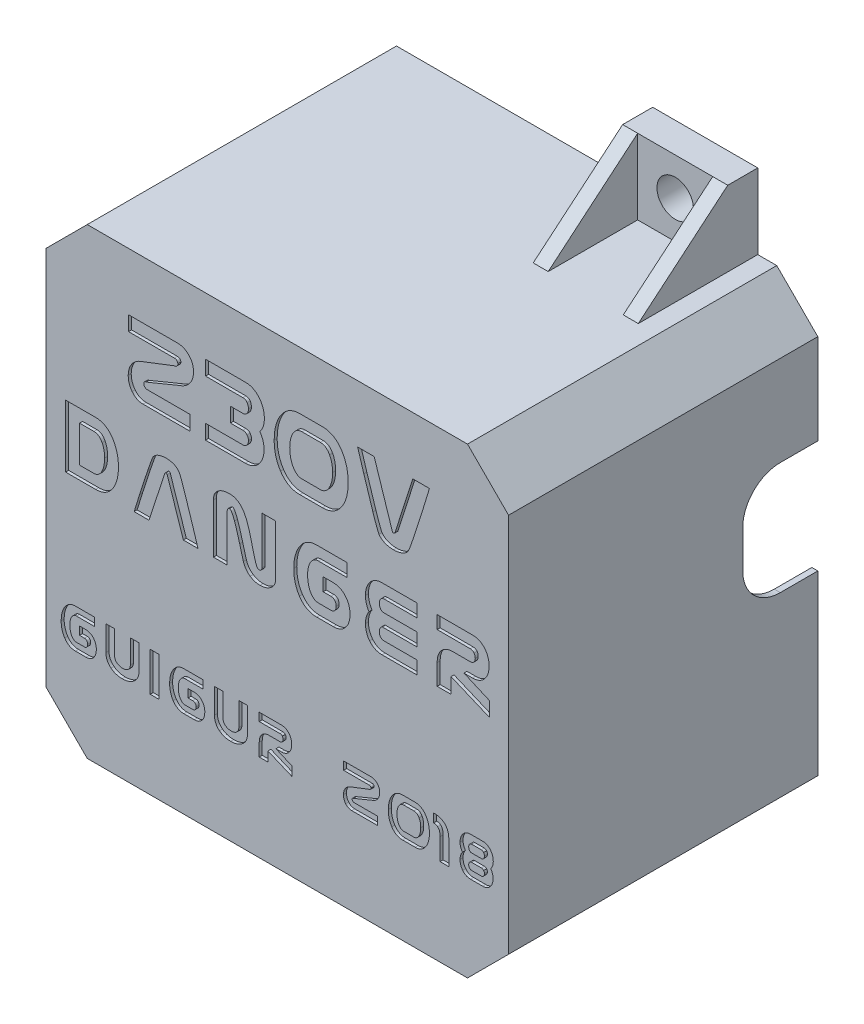
SolidWorks part; units mm, degrees
ref_plane "Plan de face" through (0, 0, 0) normal (0, 0, 1) x (1, 0, 0)
ref_plane "Plan de dessus" through (0, 0, 0) normal (0, 1, 0) x (1, 0, 0)
ref_plane "Plan de droite" through (0, 0, 0) normal (1, 0, 0) x (0, 0, -1)
sketch "Esquisse1" plane through (0, 0, 0) normal (0, 0, 1) x (1, 0, 0)
  line L0 (0.8, -55.8) -> (5.8, -60.8)
  line L1 (0, 0) -> (61.6, 0)
  line L2 (0, 0) -> (0, -61.6)
  line L3 (0, -61.6) -> (61.6, -61.6)
  line L4 (61.6, 0) -> (61.6, -61.6)
  line L5 (0.8, -0.8) -> (60.8, -0.8)
  line L6 (0.8, -0.8) -> (0.8, -60.8)
  line L7 (0.8, -60.8) -> (60.8, -60.8)
  line L8 (60.8, -0.8) -> (60.8, -60.8)
  line L9 (55.8, -60.8) -> (60.8, -55.8)
  line L10 (55.8, -0.8) -> (60.8, -5.8)
  line L11 (0.8, -5.8) -> (5.8, -0.8)
  line L12 (56.1314, 0) -> (61.6, -5.4686)
  line L13 (56.1314, -61.6) -> (61.6, -56.1314)
  line L14 (5.4686, -61.6) -> (0, -56.1314)
  line L15 (0, -5.4686) -> (5.4686, 0)
  dimension "D1" = 0.8
  dimension "D2" = 60
  dimension "D3" = 60
  dimension "D4" = 0.8
  dimension "D5" = 0.8
  dimension "D6" = 0.8
  dimension "D7" = 45
  dimension "D8" = 5
  dimension "D9" = 0.8
  dimension "D10" = 5
  dimension "D11" = 45
  dimension "D12" = 0.8
  dimension "D13" = 5
  dimension "D14" = 5
  dimension "D15" = 0.8
  dimension "D16" = 0.8
extrude "Boss.-Extru.1" add sketch "Esquisse1" along normal blind 40 contours L15 L2 L14 L6 | L14 L7 L0 L6 | L14 L3 L13 L7 | L7 L13 L8 L9 | L8 L13 L4 L12 | L12 L5 L10 L8 | L15 L5 L12 L1 | L15 L6 L11 L5 region at (0.4021, -30.8, 0) region at (3.0292, -58.5708, 0) region at (30.8, -61.1979, 0) region at (3.0292, -3.0292, 0) region at (58.5708, -58.5708, 0) region at (30.8, -0.4021, 0) region at (61.1979, -30.8, 0) region at (58.5708, -3.0292, 0)
sketch "Esquisse2" plane through (0, 0, 40) normal (0, 0, 1) x (1, 0, 0)
  line L0 (56.1314, 0) -> (61.6, -5.4686)
  line L1 (0, 0) -> (61.6, 0)
  line L2 (0, 0) -> (0, -61.6)
  line L3 (0, -61.6) -> (61.6, -61.6)
  line L4 (61.6, 0) -> (61.6, -61.6)
  line L5 (61.6, -56.1314) -> (56.1314, -61.6)
  line L6 (5.4686, -61.6) -> (0, -56.1314)
  line L7 (0, -5.4686) -> (5.4686, 0)
  line M5 (56.1314, -61.6) -> (61.6, -56.1314)
  line M6 (61.6, -56.1314) -> (61.6, -5.4686)
  line M7 (61.6, -5.4686) -> (56.1314, 0)
  line M8 (56.1314, 0) -> (5.4686, 0)
  line M9 (5.4686, 0) -> (0, -5.4686)
  line M10 (0, -5.4686) -> (0, -56.1314)
  line M11 (0, -56.1314) -> (5.4686, -61.6)
  line M12 (5.4686, -61.6) -> (56.1314, -61.6)
  line M13 (60.8, -5.8) -> (60.8, -55.8)
  line M14 (60.8, -55.8) -> (55.8, -60.8)
  line M15 (55.8, -60.8) -> (5.8, -60.8)
  line M16 (5.8, -60.8) -> (0.8, -55.8)
  line M17 (0.8, -55.8) -> (0.8, -5.8)
  line M18 (0.8, -5.8) -> (5.8, -0.8)
  line M19 (5.8, -0.8) -> (55.8, -0.8)
  line M20 (55.8, -0.8) -> (60.8, -5.8)
  dimension "D1" = 61.6
  dimension "D2" = 61.6
extrude "Boss.-Extru.2" add sketch "Esquisse2" along normal blind 1.2 contours M13 M20 M19 M18 M17 M16 M15 M14 | M12 M5 M6 M7 M8 M9 M10 M11 M20 M13 M14 M15 M16 M17 M18 M19 region at (58.8041, -2.7959, 40) region at (30.8, -30.8, 40)
sketch "Esquisse3" plane through (61.6, 0, 0) normal (1, 0, 0) x (0, 0, -1)
  line L0 (0, -5.4686) -> (0, -56.1314) construction
  line L1 (0, -32.5) -> (-5, -32.5)
  line L2 (0, -32.5) -> (0, -17.5)
  line L3 (0, -17.5) -> (-5, -17.5)
  line L4 (-10, -27.5) -> (-10, -22.5)
  arc A0 (-5, -32.5) -> (-10, -27.5) centre (-5, -27.5) cw
  arc A1 (-5, -17.5) -> (-10, -22.5) centre (-5, -22.5) ccw
  point P8 (-10, -32.5)
  point P11 (-10, -17.5)
  point P12 (0, -25)
  dimension "D3" = 5
  dimension "D1" = 15
  dimension "D2" = 10
  dimension "D4" = 25
extrude "Enlèv. mat.-Extru.1" cut sketch "Esquisse3" against normal blind 0.8
sketch "Esquisse4" plane through (0, -61.6, 0) normal (0, -1, 0) x (1, 0, 0)
  line L0 (5.4686, 0) -> (56.1314, 0) construction
  line L1 (23.3, 0) -> (38.3, 0)
  line L2 (23.3, 0) -> (23.3, 20)
  line L3 (28.3, 25) -> (33.3, 25)
  line L4 (38.3, 0) -> (38.3, 20)
  line L5 (5.4686, 41.2) -> (56.1314, 41.2) construction
  arc A0 (38.3, 20) -> (33.3, 25) centre (33.3, 20) ccw
  arc A1 (28.3, 25) -> (23.3, 20) centre (28.3, 20) ccw
  point P6 (30.8, 25)
  point P9 (30.8, 41.2)
  point P14 (23.3, 25)
  dimension "D3" = 5
  dimension "D1" = 25
  dimension "D2" = 15
extrude "Enlèv. mat.-Extru.2" cut sketch "Esquisse4" against normal blind 0.8
sketch "Esquisse5" plane through (0, 0, 41.2) normal (0, 0, 1) x (1, 0, 0)
  line L0 (0, -17) -> (61.6, -17) construction
  line L1 (0, -5.4686) -> (0, -56.1314) construction
  line L2 (61.6, -56.1314) -> (61.6, -5.4686) construction
  line L3 (0, -30) -> (61.6, -30) construction
  line L4 (56.1314, 0) -> (5.4686, 0) construction
  line L5 (0, -50) -> (61.6, -50) construction
  text T0 "230V" font "Nasalization" height in points 36
  text T1 "DANGER" font "Nasalization" height in points 32
  text T2 "GUIGUR 2018" font "Nasalization" height in points 20
  dimension "D1" = 17
  dimension "D2" = 30
  dimension "D3" = 50
extrude "Enlèv. mat.-Extru.3" cut sketch "Esquisse5" against normal blind 0.4
ref_plane "Plan1" through (56.1314, 0, 0) normal (1, 0, 0) x (0, 0, -1)
sketch "Esquisse7" plane through (0, 0, 0) normal (0, 0, -1) x (-1, 0, 0)
  line L0 (-5.4686, 0) -> (-56.1314, 0) construction
  line L1 (-51.6, 0) -> (-41.6, 0)
  line L2 (-51.6, 0) -> (-51.6, 10)
  line L3 (-51.6, 10) -> (-41.6, 10)
  line L4 (-41.6, 0) -> (-41.6, 10)
  circle A0 centre (-46.6, 5) radius 2.4316
  point P6 (-46.6, 10)
  point P10 (-41.6, 5)
  dimension "D1" = 10
  dimension "D2" = 10
  dimension "D3" = 15
extrude "Boss.-Extru.3" add sketch "Esquisse7" against normal blind 4
ref_plane "Plan2" through (46.6, 0, 0) normal (1, 0, 0) x (0, 0, -1)
sketch "Esquisse8" plane through (51.6, 0, 0) normal (1, 0, 0) x (0, 0, -1)
  line L0 (-4, 10) -> (-15.9175, 0)
  line L1 (-15.9175, 0) -> (0, 0)
  line L2 (0, 0) -> (0, 10)
  line L3 (0, 10) -> (0, 0) construction
  line L4 (0, 10) -> (-4, 10)
  dimension "D1" = 50
extrude "Boss.-Extru.4" add sketch "Esquisse8" along normal blind 2
mirror "Symétrie1" about plane through (46.6, 0, 0) normal (1, 0, 0) of "Boss.-Extru.4"
ref_plane "Plan3" through (0, -30.8, 0) normal (0, -1, 0) x (-1, 0, 0)
ref_plane "Plan4" through (30.8, 0, 0) normal (1, 0, 0) x (0, 0, -1)
ref_axis "Axe1" through (30.8, -30.8, -2.06) along (0, 0, 1)
pattern_circular "Répétition circulaire1" count 2 every 180 about axis through (30.8, -30.8, -2.06) along (0, 0, 1) of "Symétrie1", "Boss.-Extru.4", "Boss.-Extru.3"
